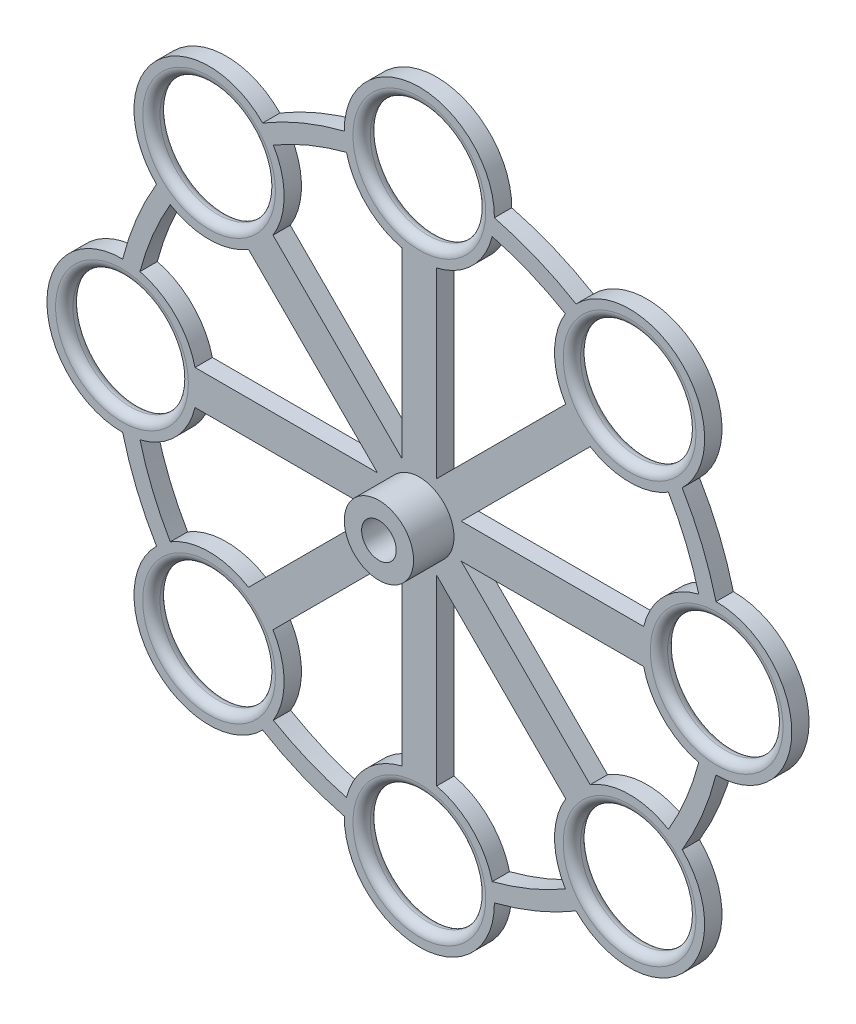
SolidWorks part; units mm, degrees
ref_plane "Alzado" through (0, 0, 0) normal (0, 0, 1) x (1, 0, 0)
ref_plane "Planta" through (0, 0, 0) normal (0, 1, 0) x (1, 0, 0)
ref_plane "Vista lateral" through (0, 0, 0) normal (1, 0, 0) x (0, 0, -1)
sketch "Croquis1" plane through (0, 0, 0) normal (0, 0, 1) x (1, 0, 0)
  line L0 (-7.2426, 3) -> (-38.8509, 3)
  line L1 (-7.2426, 3) -> (-29.593, 25.3504)
  line L4 (-7.2429, -3) -> (-29.5939, -25.3499)
  line L5 (-7.2429, -3) -> (-38.8509, -3)
  line L6 (-3, -7.2424) -> (-3, -38.8509)
  line L23 (-3, -7.2424) -> (-25.3509, -29.5922)
  line L24 (3, -7.2426) -> (25.3504, -29.593)
  line L25 (3, -7.2426) -> (3, -38.8509)
  line L26 (7.2424, -3) -> (38.8509, -3)
  line L27 (7.2424, -3) -> (29.5922, -25.3509)
  line L28 (7.2424, 3) -> (29.5922, 25.3509)
  line L29 (7.2424, 3) -> (38.8509, 3)
  line L30 (3, 7.2424) -> (3, 38.8509)
  line L31 (3, 7.2424) -> (25.3509, 29.5922)
  line L32 (-3, 7.2426) -> (-25.3504, 29.593)
  line L33 (-3, 7.2426) -> (-3, 38.8509)
  circle A0 centre (0, 0) radius 3
  arc A2 (-43.1345, 25.2867) -> (-48.3811, 12.6203) centre (0, 0) ccw
  arc A3 (-43.1345, 25.2867) -> (-29.593, 25.3504) centre (-36.416, 36.416) ccw
  arc A4 (-45.5239, 27.1399) -> (-51.3811, 12.9995) centre (0, 0) ccw
  circle A5 centre (0, 51.5) radius 10
  arc A6 (-12.6203, 48.3811) -> (-3, 38.8509) centre (0, 51.5) ccw
  circle A7 centre (-36.416, 36.416) radius 10
  arc A8 (-27.1399, 45.5239) -> (-45.5239, 27.1399) centre (-36.416, 36.416) ccw
  circle A9 centre (-51.5, 0) radius 10
  arc A10 (-51.3811, 12.9995) -> (-51.3811, -12.9995) centre (-51.5, 0) ccw
  circle A11 centre (-36.416, -36.416) radius 10
  arc A12 (-45.5239, -27.1399) -> (-27.1399, -45.5239) centre (-36.416, -36.416) ccw
  circle A13 centre (0, -51.5) radius 10
  arc A14 (-12.9995, -51.3811) -> (12.9995, -51.3811) centre (0, -51.5) ccw
  circle A15 centre (36.416, -36.416) radius 10
  arc A16 (25.3504, -29.593) -> (25.2867, -43.1345) centre (36.416, -36.416) ccw
  circle A17 centre (51.5, 0) radius 10
  arc A18 (38.8509, -3) -> (48.3811, -12.6203) centre (51.5, 0) ccw
  circle A19 centre (36.416, 36.416) radius 10
  arc A20 (25.2867, 43.1345) -> (25.3509, 29.5922) centre (36.416, 36.416) ccw
  arc A21 (-51.3811, -12.9995) -> (-45.5239, -27.1399) centre (0, 0) ccw
  arc A22 (-48.3811, -12.6203) -> (-43.1345, -25.2867) centre (0, 0) ccw
  arc A23 (-38.8509, 3) -> (-48.3811, 12.6203) centre (-51.5, 0) ccw
  arc A24 (-48.3811, -12.6203) -> (-38.8509, -3) centre (-51.5, 0) ccw
  arc A25 (-12.9995, 51.3811) -> (-27.1399, 45.5239) centre (0, 0) ccw
  arc A26 (-25.3504, 29.593) -> (-25.2867, 43.1345) centre (-36.416, 36.416) ccw
  arc A27 (-25.2867, -43.1345) -> (-12.6203, -48.3811) centre (0, 0) ccw
  arc A28 (-27.1399, -45.5239) -> (-12.9995, -51.3811) centre (0, 0) ccw
  arc A29 (-12.6203, 48.3811) -> (-25.2867, 43.1345) centre (0, 0) ccw
  arc A30 (-29.5939, -25.3499) -> (-43.1345, -25.2867) centre (-36.416, -36.416) ccw
  arc A31 (-25.2867, -43.1345) -> (-25.3509, -29.5922) centre (-36.416, -36.416) ccw
  arc A32 (12.6203, -48.3811) -> (25.2867, -43.1345) centre (0, 0) ccw
  arc A33 (12.9995, 51.3811) -> (-12.9995, 51.3811) centre (0, 51.5) ccw
  arc A34 (3, 38.8509) -> (12.6203, 48.3811) centre (0, 51.5) ccw
  arc A35 (12.9995, -51.3811) -> (27.1399, -45.5239) centre (0, 0) ccw
  arc A36 (-3, -38.8509) -> (-12.6203, -48.3811) centre (0, -51.5) ccw
  arc A37 (12.6203, -48.3811) -> (3, -38.8509) centre (0, -51.5) ccw
  arc A38 (43.1345, -25.2867) -> (48.3811, -12.6203) centre (0, 0) ccw
  arc A39 (45.5239, -27.1399) -> (51.3811, -12.9995) centre (0, 0) ccw
  arc A40 (27.1399, -45.5239) -> (45.5239, -27.1399) centre (36.416, -36.416) ccw
  arc A41 (43.1345, -25.2867) -> (29.5922, -25.3509) centre (36.416, -36.416) ccw
  arc A42 (48.3811, 12.6203) -> (43.1345, 25.2867) centre (0, 0) ccw
  arc A43 (51.3811, 12.9995) -> (45.5239, 27.1399) centre (0, 0) ccw
  arc A44 (51.3811, -12.9995) -> (51.3811, 12.9995) centre (51.5, 0) ccw
  arc A45 (48.3811, 12.6203) -> (38.8509, 3) centre (51.5, 0) ccw
  arc A46 (25.2867, 43.1345) -> (12.6203, 48.3811) centre (0, 0) ccw
  arc A47 (27.1399, 45.5239) -> (12.9995, 51.3811) centre (0, 0) ccw
  arc A48 (45.5239, 27.1399) -> (27.1399, 45.5239) centre (36.416, 36.416) ccw
  arc A49 (29.5922, 25.3509) -> (43.1345, 25.2867) centre (36.416, 36.416) ccw
  point P3 (0, 0)
extrude "Saliente-Extruir2" add sketch "Croquis1" along normal blind 3
fillet "Redondeo1" radius 1.5 1 edges at (61.5, 0, 3)
fillet "Redondeo2" radius 1.5 1 edges at (61.5, 0, 0)
fillet "Redondeo3" radius 1.5 1 edges at (46.416, -36.416, 0)
fillet "Redondeo4" radius 1.5 1 edges at (46.416, -36.416, 3)
fillet "Redondeo5" radius 1.5 1 edges at (10, -51.5, 0)
fillet "Redondeo6" radius 1.5 1 edges at (10, -51.5, 3)
fillet "Redondeo7" radius 1.5 1 edges at (-26.416, -36.416, 0)
fillet "Redondeo8" radius 1.5 1 edges at (-26.416, -36.416, 3)
fillet "Redondeo9" radius 1.5 1 edges at (-41.5, 0, 0)
fillet "Redondeo10" radius 1.5 1 edges at (-41.5, 0, 3)
fillet "Redondeo11" radius 1.5 1 edges at (-26.416, 36.416, 0)
fillet "Redondeo12" radius 1.5 1 edges at (-26.416, 36.416, 3)
fillet "Redondeo13" radius 1.5 1 edges at (10, 51.5, 0)
fillet "Redondeo14" radius 1.5 1 edges at (10, 51.5, 3)
fillet "Redondeo15" radius 1.5 1 edges at (46.416, 36.416, 0)
fillet "Redondeo16" radius 1.5 1 edges at (46.416, 36.416, 3)
sketch "Croquis18" plane through (0, 0, 3) normal (0, 0, 1) x (1, 0, 0)
  circle A0 centre (0, 0) radius 3
  circle A1 centre (0, 0) radius 6
extrude "Saliente-Extruir5" add sketch "Croquis18" along normal blind 7
